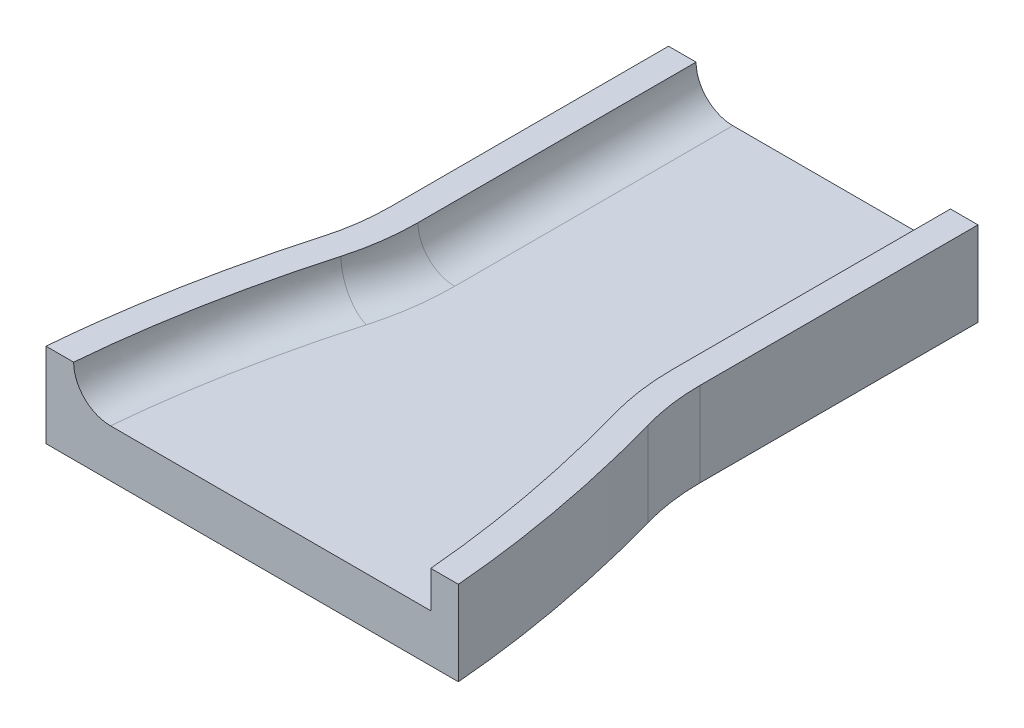
SolidWorks part; units mm, degrees
ref_plane "Alzado" through (0, 0, 0) normal (0, 0, 1) x (1, 0, 0)
ref_plane "Planta" through (0, 0, 0) normal (0, 1, 0) x (1, 0, 0)
ref_plane "Vista lateral" through (0, 0, 0) normal (1, 0, 0) x (0, 0, -1)
sketch "Croquis2" plane through (0, 0, 0) normal (0, 1, 0) x (1, 0, 0)
  line L0 (-34.6199, 80.9973) -> (35.4836, 80.9973)
  line L1 (-49.5506, -74.5192) -> (50.4144, -74.5192)
  line L2 (50.4144, -74.5192) -> (56.5832, -74.5192)
  line L3 (35.4836, 80.9973) -> (42.5674, 80.9973)
  line L4 (42.5674, 80.9973) -> (42.5674, 5.2721)
  line L5 (-49.5506, -74.5192) -> (-55.7195, -74.5192)
  line L6 (-34.6199, 80.9973) -> (-41.7037, 80.9973)
  line L7 (-41.7037, 80.9973) -> (-41.7037, 5.2721)
  arc A0 (44.8459, -11.1055) -> (42.5674, 5.2721) centre (102.5674, 5.2721) cw
  arc A1 (-43.9821, -11.1055) -> (-41.7037, 5.2721) centre (-101.7037, 5.2721) ccw
  spline S0 degree 3 poles (56.5832, -74.5192) (54.897, -53.8979) (50.7074, -31.7639) (44.8459, -11.1055) knots 0 0 0 0 0.769012 0.769012 0.769012 0.769012
  spline S1 degree 3 poles (-55.7195, -74.5192) (-54.0332, -53.8979) (-49.8437, -31.7639) (-43.9821, -11.1055) knots 0 0 0 0 0.769012 0.769012 0.769012 0.769012
  point P10 (0.4319, -74.5192)
  point P17 (0.4319, 80.9973)
  dimension "D1" = 60
extrude "Saliente-Extruir1" add sketch "Croquis2" along normal blind 13 contours L0 L3 L4 A0 S0 L2 L1 L5 S1 A1 L7 L6
sketch "Croquis3" plane through (0, 13, 0) normal (0, 1, 0) x (1, 0, 0)
  line L4 (-55.7195, -74.5192) -> (-48.1937, -74.5192)
  line L5 (-41.7037, 5.2721) -> (-41.7037, 80.9973)
  line L7 (-41.7037, 5.2721) -> (-41.7037, 80.9973)
  line L8 (56.5832, -74.5192) -> (49.0575, -74.5192)
  line L9 (42.5674, 5.2721) -> (42.5674, 80.9973)
  line L10 (42.5674, 5.2721) -> (42.5674, 80.9973)
  line L11 (56.5832, -74.5192) -> (-55.7195, -74.5192) construction
  line L12 (35.0674, 80.9973) -> (42.5674, 80.9973)
  line L13 (-41.7037, 80.9973) -> (-34.2037, 80.9973)
  line L17 (-34.2037, 80.9973) -> (-34.2037, 5.2721)
  line L18 (-34.2037, 80.9973) -> (-34.2037, 5.2721)
  line L22 (35.0674, 80.9973) -> (35.0674, 5.2721)
  line L23 (35.0674, 80.9973) -> (35.0674, 5.2721)
  arc A4 (42.5674, 5.2721) -> (44.8459, -11.1055) centre (102.5674, 5.2721) ccw
  arc A5 (42.5674, 5.2721) -> (44.8459, -11.1055) centre (102.5674, 5.2721) ccw
  arc A6 (-43.9821, -11.1055) -> (-41.7037, 5.2721) centre (-101.7037, 5.2721) ccw
  arc A7 (-43.9821, -11.1055) -> (-41.7037, 5.2721) centre (-101.7037, 5.2721) ccw
  arc A15 (-36.7669, -13.1527) -> (-34.2037, 5.2721) centre (-101.7037, 5.2721) ccw
  arc A16 (-36.7669, -13.1527) -> (-34.2037, 5.2721) centre (-101.7037, 5.2721) ccw
  arc A19 (35.0674, 5.2721) -> (37.6307, -13.1527) centre (102.5674, 5.2721) ccw
  arc A20 (35.0674, 5.2721) -> (37.6307, -13.1527) centre (102.5674, 5.2721) ccw
  spline S4 degree 3 poles (-1773.7885, 3458.4874) (1592.2648, -4644.0882) (-993.1056, 4739.3757) (372.9434, -3982.0495) knots -8.239108 -8.239108 -8.239108 -8.239108 9.323036 9.323036 9.323036 9.323036 only from (56.5832, -74.5192) to (44.8459, -11.1055)
  spline S5 degree 3 poles (56.5832, -74.5192) (54.897, -53.8979) (50.7074, -31.7639) (44.8459, -11.1055) knots 0 0 0 0 0.769012 0.769012 0.769012 0.769012
  spline S7 degree 3 poles (1774.6522, 3458.4874) (-1591.401, -4644.0882) (993.9694, 4739.3757) (-372.0796, -3982.0495) knots -8.239108 -8.239108 -8.239108 -8.239108 9.323036 9.323036 9.323036 9.323036 only from (-55.7195, -74.5192) to (-43.9821, -11.1055)
  spline S8 degree 3 poles (-55.7195, -74.5192) (-54.0332, -53.8979) (-49.8437, -31.7639) (-43.9821, -11.1055) knots 0 0 0 0 0.769012 0.769012 0.769012 0.769012
  spline S11 degree 3 poles (12.2896, -1011.9456) (139.5867, 284.3085) (-13.874, 117.8475) (-72.448, -196.768) (8.4817, -345.6111) (508.2554, 755.7055) knots -7.244544 -7.244544 -7.244544 -7.244544 0.5 0.5 7.791597 7.791597 7.791597 7.791597 only from (-36.7669, -13.1527) to (-48.2444, -75.1305)
  spline S12 degree 3 poles (-36.7669, -13.1527) (-39.6338, -23.2567) (-42.0955, -33.737) (-45.9515, -54.4485) (-47.3662, -64.6812) (-48.1937, -74.5192) knots 0 0 0 0 0.5 0.5 0.989847 0.989847 0.989847 0.989847
  spline S14 degree 3 poles (-11.4259, -1011.9456) (-138.723, 284.3085) (14.7378, 117.8475) (73.3117, -196.768) (-7.6179, -345.6111) (-507.3916, 755.7055) knots -7.244544 -7.244544 -7.244544 -7.244544 0.5 0.5 7.791597 7.791597 7.791597 7.791597 only from (37.6307, -13.1527) to (49.1082, -75.1305)
  spline S15 degree 3 poles (37.6307, -13.1527) (40.4975, -23.2567) (42.9592, -33.737) (46.8152, -54.4485) (48.23, -64.6812) (49.0575, -74.5192) knots 0 0 0 0 0.5 0.5 0.989847 0.989847 0.989847 0.989847
  dimension "D3" = 7.5257
  dimension "D6" = 7.5257
  dimension "D1" = 7.5
  dimension "D2" = 7.5
  dimension "D4" = 0
  dimension "D5" = 0
extrude "Saliente-Extruir2" add sketch "Croquis3" along normal blind 10
fillet "Redondeo1" radius 10 3 edges at (-34.2037, 13, -43.1347)
